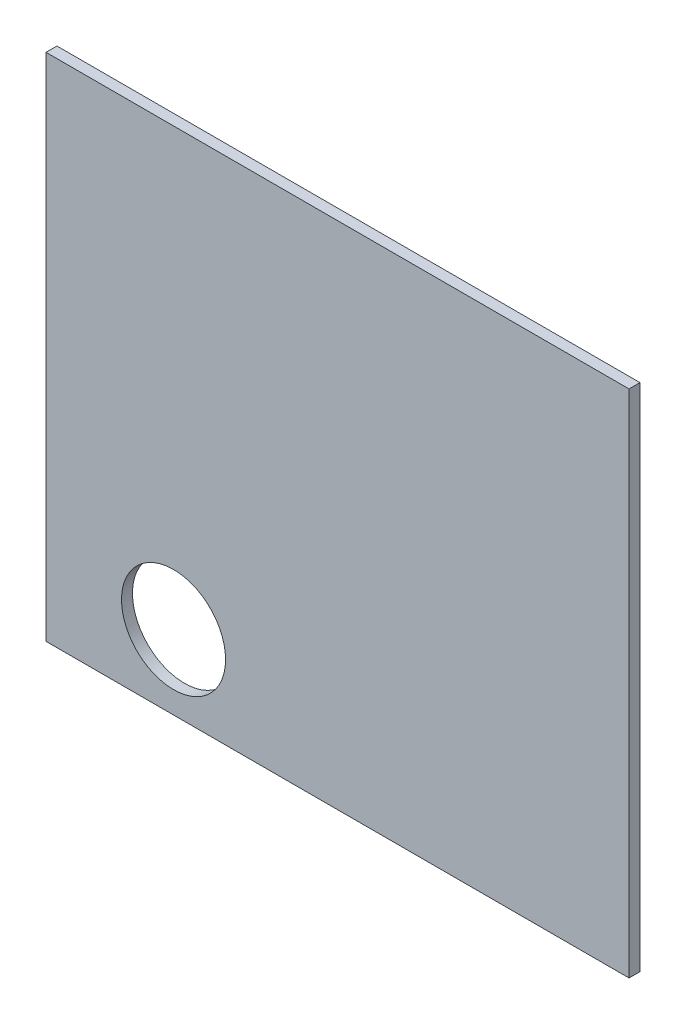
SolidWorks part; units mm, degrees
ref_plane "Front Plane" through (0, 0, 0) normal (0, 0, 1) x (1, 0, 0)
ref_plane "Top Plane" through (0, 0, 0) normal (0, 1, 0) x (1, 0, 0)
ref_plane "Right Plane" through (0, 0, 0) normal (1, 0, 0) x (0, 0, -1)
sketch "Sketch1" plane through (0, 0, 0) normal (0, 0, 1) x (1, 0, 0)
  line L1 (0, 0) -> (160, 0)
  line L2 (0, 0) -> (0, 140)
  line L3 (0, 140) -> (160, 140)
  line L4 (160, 0) -> (160, 140)
  dimension "D1" = 160
  dimension "D2" = 140
extrude "Boss-Extrude1" add sketch "Sketch1" along normal blind 3
sketch "Sketch2" plane through (0, 0, 3) normal (0, 0, 1) x (1, 0, 0)
  line L0 (160, 140) -> (0, 140) construction
  line L2 (0, 140) -> (0, 0) construction
  circle A0 centre (35, 20.31) radius 14.275
  dimension "D1" = 28.55
  dimension "D2" = 35
  dimension "D3" = 119.69
extrude "Cut-Extrude1" cut sketch "Sketch2" against normal blind 3
